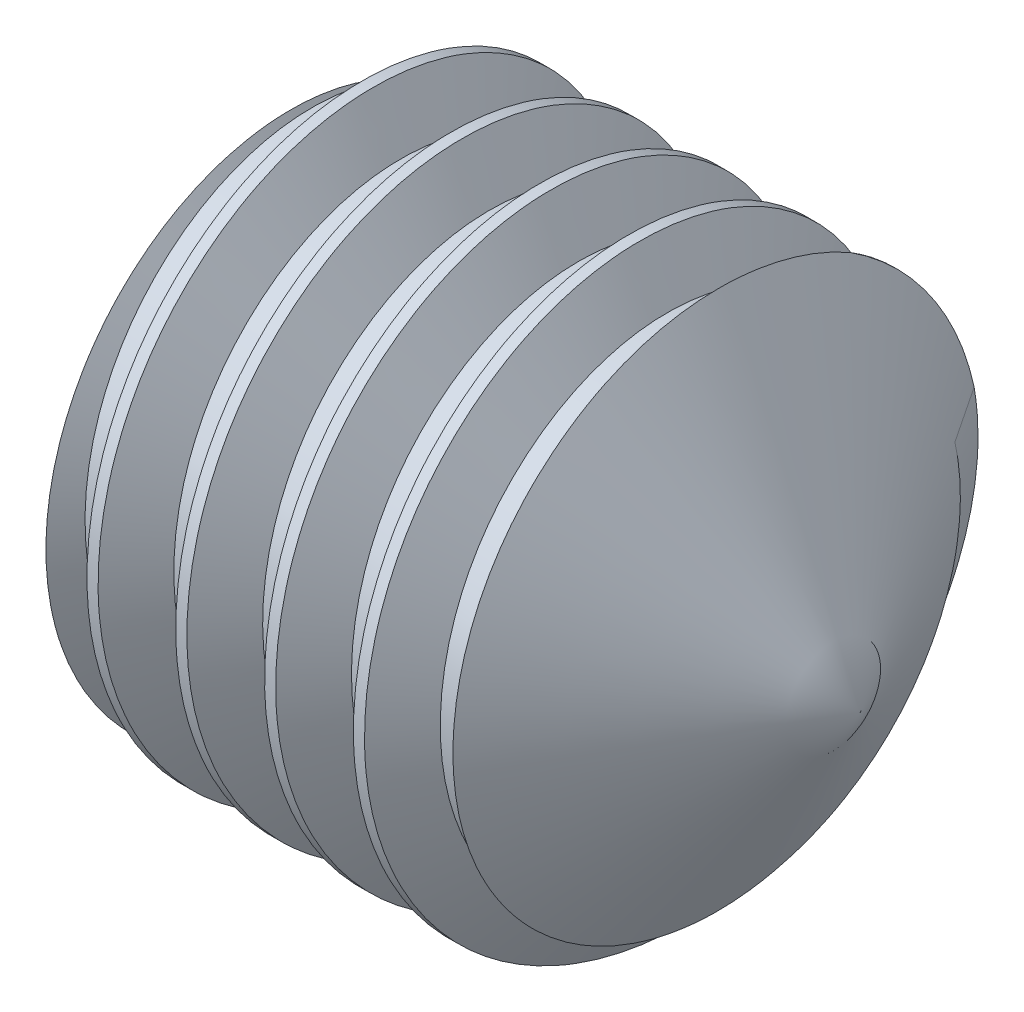
SolidWorks part; units mm, degrees
revolve "BaseBody" add sketch "BodySke" angle 360 about L5 other way angle 60
sketch "BodySke" plane through (0, 0, 0) normal (0, 0, 1) x (1, 0, 0)
  line L0 (0, 0) -> (0, 3.3095)
  line L1 (0, 3.3095) -> (0.3987, 4)
  line L2 (0.3987, 4) -> (5.6906, 4)
  line L3 (5.6906, 4) -> (8, 0)
  line L4 (8, 0) -> (0, 0)
  line L5 (-12.7, 0) -> (88.9, 0) construction
  line L6 (5.6906, -4) -> (8, 0) construction
  line L7 (0.625, 15.875) -> (0.625, -3.175) construction
  line L8 (0, -3.3095) -> (0.3987, -4) construction
  dimension "Cone_ang" = 120
  dimension "Length" = 8
  dimension "Diameter" = 8
cosmetic thread "ThreadCosmetic" parameters "Thread_minor"=6.619
material "A286 Iron Base Superalloy"
ref_plane "Plane1" through (0, 0, 0) normal (0, 0, 1) x (1, 0, 0)
ref_plane "Plane2" through (0, 0, 0) normal (0, 1, 0) x (1, 0, 0)
ref_plane "Plane3" through (0, 0, 0) normal (1, 0, 0) x (0, 0, -1)
other "Configuration Table"
sketch "Sketch2" plane through (0, 0, 0) normal (-1, 0, 0) x (0, 0, 1)
  line L0 (1.1547, 2) -> (-1.1547, 2)
  line L1 (-1.1547, 2) -> (-2.3094, 0)
  line L2 (1.1547, 2) -> (2.3094, 0)
  line L3 (1.1547, -2) -> (2.3094, 0)
  line L4 (1.1547, -2) -> (-1.1547, -2)
  line L5 (-1.1547, -2) -> (-2.3094, 0)
  dimension "D2" = 2
  dimension "D3" = 2
  dimension "D1" = 2.3094
  dimension "D4" = 2
extrude "Hex" cut sketch "Sketch2" against normal blind 3
sketch "ThdSchSke" plane through (0, 0, 0) normal (0, 0, 1) x (1, 0, 0)
  line L0 (0.3987, -3.3095) -> (-0.0848, -4)
  line L1 (0.3987, -3.3095) -> (0.8822, -4)
  line L2 (0.8822, -4) -> (0.8822, -5)
  line L3 (-3.175, 0) -> (5.1513, 0) construction
  line L4 (0.3987, 4) -> (0.3987, -4) construction
  line L5 (0.8822, -5) -> (-0.0848, -5)
  line L6 (-0.0848, -5) -> (-0.0848, -4)
  dimension "Thread_minor" = 6.619
  dimension "Diameter" = 8
revolve "ThreadSchematic" [suppressed] cut sketch "ThdSchSke" angle 360 about L3
pattern_linear "ThdSchPat" [suppressed]
thread "Thread2" pitch 1.25 method cut profile "Thread Profile2" start angle 0, offset 1, length 10, pitch 1.25, diameter 8
ref_plane "Plane5" through (-0.6013, 0, -4) normal (0, -1, 0) x (0, 0, -1)
sketch "Thread Profile2" plane through (-0.6013, 0, -4) normal (0, -1, 0) x (0, 0, -1)
  line L0 (0, 0) -> (0, 1.25) construction
  line L11 (0, 0) -> (0, 1.0937)
  line L12 (0, 1.0937) -> (-0.6766, 0.7031)
  line L13 (-0.6766, 0.7031) -> (-0.6766, 0.3906)
  line L15 (-0.6766, 0.3906) -> (0, 0)
  line L17 (-0.6766, 0.5469) -> (0, 0.5469) construction
  point P2 (0, 0)
  dimension "Pitch" = 1.25
  dimension "Profile_Angle" = 60
  dimension "Profile_Land" = 0.3125
  dimension "Profile_Height" = 0.6766
equation "\"D2@Sketch2\" = \"Hex_size@Sketch2\" / 2"
equation "\"D3@Sketch2\" = \"Hex_size@Sketch2\" / 2"
equation "\"Thread_minor@ThreadCosmetic\"=\"Minor_dia@BodySke\""
equation "\"Thread_minor@ThdSchSke\" = \"Thread_minor@ThreadCosmetic\""
equation "\"Diameter@ThdSchSke\" = \"Diameter@BodySke\""
equation "\"Overcut@ThdSchSke\" = \"Diameter@BodySke\" * 1.25"
equation "\"Num_threads@ThdSchPat\" = int( (\"Length@BodySke\" - ( ( ( \"Diameter@BodySke\" - \"Minor_dia@BodySke\" ) * 0.5 ) / tan( \"Drive_ch_ang@BodySke\" * 0.017453292 ) ) - ( ( \"Diameter@BodySke\" * 0.5 ) / tan( \"Cone_ang@BodySke\" * 0.008726646 ) ) ) / \"Advance@BodySke\" + 0.999 )  + 1"
equation "\"Advance@ThdSchPat\" = (\"Length@BodySke\" - ( ( ( \"Diameter@BodySke\" - \"Minor_dia@BodySke\" ) * 0.5 ) / tan( \"Drive_ch_ang@BodySke\" * 0.017453292 ) ) - ( ( \"Diameter@BodySke\" * 0.5 ) / tan( \"Cone_ang@BodySke\" * 0.008726646 ) ) ) /  (\"Num_threads@ThdSchPat\" - 1) 'relax it"
equation "' \"Num_threads@ThdSchPat\" = \"Num_threads@ThdSchPat\" - sgn( \"Num_threads@ThdSchPat\" - 1) '---chamfered tips only---"
